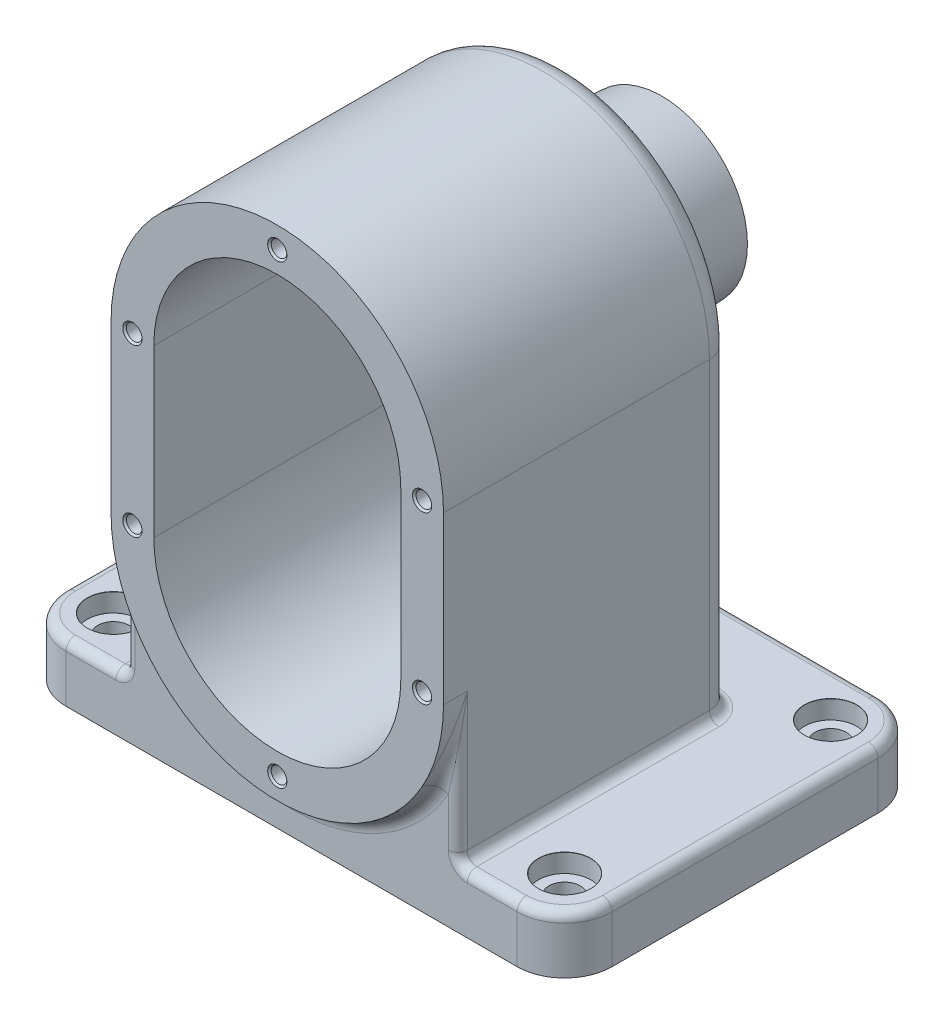
SolidWorks part; units mm, degrees
ref_plane "Front Plane" through (0, 0, 0) normal (0, 0, 1) x (1, 0, 0)
ref_plane "Top Plane" through (0, 0, 0) normal (0, 1, 0) x (1, 0, 0)
ref_plane "Right Plane" through (0, 0, 0) normal (1, 0, 0) x (0, 0, -1)
sketch "Sketch2" plane through (0, 0, 0) normal (0, 0, 1) x (1, 0, 0)
  line L0 (0, -17.5) -> (0, 17.5) construction
  line L1 (-35, -17.5) -> (-35, 17.5)
  line L2 (35, -17.5) -> (35, 17.5)
  arc A0 (-35, -17.5) -> (35, -17.5) centre (0, -17.5) ccw
  arc A1 (35, 17.5) -> (-35, 17.5) centre (0, 17.5) ccw
  point P2 (0, 0)
  dimension "D1" = 35
  dimension "D2" = 35
extrude "Boss-Extrude3" add sketch "Sketch2" along normal mid plane 58
shell "Shell9" thickness 9 removed face at (0, 0, 29)
sketch "Sketch3" plane through (0, 0, 0) normal (1, 0, 0) x (0, 0, -1)
  line L0 (29, 17.5) -> (49, 17.5)
  line L2 (29, -17.5) -> (29, 17.5) construction
  line L4 (49, -0.5) -> (49, 17.5)
  line L5 (29, -1.7644) -> (49, -0.5)
  line L6 (29, 17.5) -> (29, -1.7644)
  dimension "D1" = 18
  dimension "D2" = 20
revolve "Revolve1" add sketch "Sketch3" angle 360 about L0
sketch "Sketch4" plane through (0, 0, 0) normal (1, 0, 0) x (0, 0, -1)
  line L0 (20, 17.5) -> (20, 36.5489)
  line L1 (-29, 17.5) -> (29, 17.5) construction
  line L2 (20, 36.5489) -> (5, 35.5)
  line L3 (5, 35.5) -> (5, 17.5)
  line L4 (5, 17.5) -> (20, 17.5)
  line L5 (29, -1.7644) -> (29, 36.7644) construction
  line L6 (5, 35.5) -> (69.0806, 35.5) construction
  dimension "D1" = 9
  dimension "D2" = 18
  dimension "D3" = 15
  dimension "D4" = 4
revolve "Revolve2" add sketch "Sketch4" angle 360 about L4
sketch "Sketch5" plane through (0, 0, 0) normal (1, 0, 0) x (0, 0, -1)
  line L0 (20, -17.5) -> (20, -6.95)
  line L1 (-29, -17.5) -> (29, -17.5) construction
  line L2 (20, -6.95) -> (5, -8)
  line L3 (5, -8) -> (5, -17.5)
  line L4 (5, -17.5) -> (20, -17.5)
  line L5 (5, -8) -> (69.1367, -8) construction
  line L6 (29, -17.5) -> (29, 17.5) construction
  dimension "D1" = 9.5
  dimension "D2" = 15
  dimension "D3" = 10.55
  dimension "D4" = 9
revolve "Revolve4" add sketch "Sketch5" angle 360 about L4
sketch "Sketch6" plane through (0, 0, -49) normal (0, 0, -1) x (-1, 0, 0)
  circle A0 centre (0, 17.5) radius 14
  dimension "D1" = 28
extrude "Cut-Extrude1" cut sketch "Sketch6" against normal blind 15
sketch "Sketch7" plane through (0, 0, -34) normal (0, 0, -1) x (-1, 0, 0)
  circle A0 centre (0, 17.5) radius 10.5
  dimension "D1" = 21
extrude "Cut-Extrude2" cut sketch "Sketch7" against normal blind 6
sketch "Sketch8" plane through (0, 0, -28) normal (0, 0, -1) x (-1, 0, 0)
  circle A0 centre (0, 17.5) radius 9
  dimension "D1" = 18
extrude "Boss-Extrude4" add sketch "Sketch8" against normal blind 14.8
sketch "Sketch9" plane through (0, 0, -28) normal (0, 0, -1) x (-1, 0, 0)
  circle A0 centre (0, 17.5) radius 10.5
  dimension "D1" = 21
extrude "Cut-Extrude3" cut sketch "Sketch9" against normal blind 5
sketch "Sketch10" plane through (0, 0, -23) normal (0, 0, -1) x (-1, 0, 0)
  circle A0 centre (0, 17.5) radius 11
  dimension "D1" = 22
extrude "Cut-Extrude4" cut sketch "Sketch10" against normal blind 1.1
sketch "Sketch11" plane through (0, 0, -5) normal (0, 0, 1) x (1, 0, 0)
  circle A0 centre (0, 17.5) radius 10.5
  dimension "D1" = 21
extrude "Cut-Extrude5" cut sketch "Sketch11" against normal through all
sketch "Sketch12" plane through (0, 0, -5) normal (0, 0, 1) x (1, 0, 0)
  circle A0 centre (0, -17.5) radius 6
  dimension "D1" = 12
extrude "Cut-Extrude6" cut sketch "Sketch12" against normal through all both and the other way through all
sketch "Sketch15" plane through (0, 0, 29) normal (0, 0, 1) x (1, 0, 0)
  line L0 (26, -17.5) -> (26, 17.5) construction
  line L1 (-26, 17.5) -> (-26, -17.5) construction
  line L2 (35, -17.5) -> (35, 17.5)
  line L3 (-35, 17.5) -> (-35, -17.5)
  line L4 (35, -17.5) -> (35, 17.5)
  line L5 (-35, 17.5) -> (-35, -17.5)
  line L6 (26, -17.5) -> (26, 17.5)
  line L7 (-26, 17.5) -> (-26, -17.5)
  arc A0 (-26, -17.5) -> (26, -17.5) centre (0, -17.5) ccw construction
  arc A1 (26, 17.5) -> (-26, 17.5) centre (0, 17.5) ccw construction
  arc A2 (-35, -17.5) -> (35, -17.5) centre (0, -17.5) ccw
  arc A3 (35, 17.5) -> (-35, 17.5) centre (0, 17.5) ccw
  arc A4 (-35, -17.5) -> (35, -17.5) centre (0, -17.5) ccw
  arc A5 (35, 17.5) -> (-35, 17.5) centre (0, 17.5) ccw
  arc A6 (-26, -17.5) -> (26, -17.5) centre (0, -17.5) ccw
  arc A7 (26, 17.5) -> (-26, 17.5) centre (0, 17.5) ccw
  dimension "D1" = 0
extrude "Boss-Extrude6" add sketch "Sketch15" along normal blind 3
sketch "Sketch16" plane through (0, 0, 0) normal (1, 0, 0) x (0, 0, -1)
  line L0 (-32, 17.5) -> (29, 17.5) construction
  line L1 (-29, -48.5) -> (47, -48.5)
  line L2 (-29, -48.5) -> (-29, -60.5)
  line L3 (-29, -60.5) -> (47, -60.5)
  line L4 (47, -48.5) -> (47, -60.5)
  dimension "D1" = 3
  dimension "D2" = 76
  dimension "D3" = 12
  dimension "D4" = 66
extrude "Boss-Extrude7" add sketch "Sketch16" along normal mid plane 115
sketch "Sketch18" plane through (0, 0, -29) normal (0, 0, -1) x (-1, 0, 0)
  line L0 (-57.5, -48.5) -> (57.5, -48.5) construction
  line L1 (-35, -48.5) -> (35, -48.5)
  line L4 (-35, -17.5) -> (-35, -48.5)
  line L5 (35, -17.5) -> (35, -48.5)
  line L8 (-16.2481, -48.5) -> (16.2481, -48.5)
  line L9 (35, -17.5) -> (35, 17.5)
  line L10 (-35, 17.5) -> (-35, -17.5)
  line L11 (-16.2481, -48.5) -> (16.2481, -48.5)
  arc A3 (16.2481, -48.5) -> (35, -17.5) centre (0, -17.5) ccw
  arc A4 (35, 17.5) -> (-35, 17.5) centre (0, 17.5) ccw
  arc A5 (-35, -17.5) -> (-16.2481, -48.5) centre (0, -17.5) ccw
  arc A6 (16.2481, -48.5) -> (35, -17.5) centre (0, -17.5) ccw
  arc A8 (-35, -17.5) -> (-16.2481, -48.5) centre (0, -17.5) ccw
  arc M5 (16.2481, -48.5) -> (35, -17.5) centre (0, -17.5) ccw
  arc M9 (-35, -17.5) -> (-16.2481, -48.5) centre (0, -17.5) ccw
  dimension "D1" = 0
extrude "Boss-Extrude8" add sketch "Sketch18" against normal up to surface (58 mm away) contours L4 L1 M9 | L5 L1 M5 region at (29.7786, -41.2241, -29) region at (-29.7786, -41.2241, -29) up to face at (0, -53.1667, 29)
sketch "Sketch23" plane through (0, 0, -29) normal (0, 0, -1) x (-1, 0, 0)
  circle A0 centre (0, -17.5) radius 7.5
  circle A1 centre (0, -17.5) radius 6 construction
  circle A2 centre (0, -17.5) radius 6
  dimension "D1" = 15
extrude "Boss-Extrude9" add sketch "Sketch23" along normal blind 2
fillet "Fillet1" radius 10 4 edges at (-57.5, -54.5, -47) (-57.5, -54.5, 29) (57.5, -54.5, -47) (57.5, -54.5, 29)
hole_wizard "CBORE for M6 Cheese Head Screw1" positions "Sketch25" profile "Sketch26" counterbore size "M6" standard "ISO" end condition through all
sketch "Sketch25" plane through (0, -48.5, 0) normal (0, 1, 0) x (1, 0, 0)
  point P0 (-47.5, 37)
  point P3 (-47.5, -19)
  point P6 (47.5, -19)
  point P9 (47.5, 37)
sketch "Sketch26" plane through (-47.5, -48.5, -37) normal (1, 0, 0) x (0, 0, 1)
  line L0 (0, 0) -> (0, 12)
  line L1 (0, 12) -> (3.3, 12)
  line L3 (3.3, 12) -> (3.3, 3.9)
  line L4 (5.5, 3.9) -> (3.3, 3.9)
  line L5 (5.5, 3.9) -> (5.5, 0.025)
  line L6 (5.5, 0.025) -> (5.525, 0)
  line L7 (5.525, 0) -> (0, 0)
  line L8 (-5.5, 0.025) -> (-5.525, 0) construction
  line L11 (0, -6.35) -> (0, 107.95) construction
  dimension "Thru Hole Dia." = 6.6
  dimension "Thru Hole Depth" = 12
  dimension "C'Bore Dia." = 11
  dimension "C'Bore Depth" = 3.9
  dimension "Near C'Sink Dia." = 11.05
  dimension "Near C'Sink Angle" = 90
fillet "Fillet2" radius 5 3 edges at (35, -15.5, -29) (-35, -15.5, -29) (0, 52.5, -29)
fillet "Fillet3" radius 2 19 edges at (35, -33, 29) (-35, -33, 29) (41.25, -48.5, 29) (54.5711, -48.5, 26.0711) (57.5, -48.5, -9) (54.5711, -48.5, -44.0711) (-41.25, -48.5, 29) (-54.5711, -48.5, 26.0711) (-57.5, -48.5, -9) (-54.5711, -48.5, -44.0711) (-35, -48.5, 2.5) (-33.5355, -48.5, -27.5355) (35, -48.5, 2.5) (33.5355, -48.5, -27.5355) (10.55, -17.5, -20) (7.5, -17.5, -29) (19.2644, 17.5, -29) (0, -48.5, -47) (0, -48.5, -29)
sketch "Sketch27" plane through (0, 0, 32) normal (0, 0, 1) x (1, 0, 0)
  line L0 (0, 43.5) -> (0, 52.5)
  line L1 (-26, 17.5) -> (-35, 17.5)
  line L4 (26, 17.5) -> (35, 17.5)
  line L7 (0, -43.5) -> (0, -52.5)
  line L8 (-35, -17.5) -> (-26, -17.5)
  line L9 (26, -17.5) -> (35, -17.5)
  arc A0 (26, 17.5) -> (-26, 17.5) centre (0, 17.5) ccw construction
  arc A1 (35, 17.5) -> (-35, 17.5) centre (0, 17.5) ccw construction
  arc A2 (-26, -17.5) -> (26, -17.5) centre (0, -17.5) ccw construction
  arc A3 (-35, -17.5) -> (35, -17.5) centre (0, -17.5) ccw construction
  point P16 (0, 48)
  point P17 (-30.5, 17.5)
  point P18 (-30.5, -17.5)
  point P19 (0, -48)
  point P28 (30.5, -17.5)
  point P37 (30.5, 17.5)
hole_wizard "M4 Tapped Hole1" positions "3DSketch1" profile "Sketch29" tap size "M4" standard "ISO"
sketch3d "3DSketch1"
  point P0 (0, 48, 32)
  point P3 (30.5, 17.5, 32)
  point P6 (30.5, -17.5, 32)
  point P9 (0, -48, 32)
  point P12 (-30.5, -17.5, 32)
  point P15 (-30.5, 17.5, 32)
sketch "Sketch29" plane through (0, 48, 32) normal (1, 0, 0) x (0, -1, 0)
  line L0 (0, 0) -> (0, 13.9914)
  line L1 (0, 13.9914) -> (1.65, 13)
  line L2 (1.65, 13) -> (1.65, 0.375)
  line L3 (1.65, 0.375) -> (2.025, 0)
  line L5 (2.025, 0) -> (0, 0)
  line L6 (-1.65, 0.375) -> (-2.025, 0) construction
  line L10 (0, 13.9914) -> (-1.65, 13) construction
  line L11 (0, -6.35) -> (0, 107.95) construction
  dimension "Tap Drill Dia." = 3.3
  dimension "Tap Drill Depth" = 13
  dimension "Near C'Sink Dia." = 4.05
  dimension "Near C'Sink Angle" = 90
  dimension "Drill Angle" = 118
cosmetic thread "Hole Thread1" parameters "D1"=10, "D2"=4
cosmetic thread "Hole Thread2" parameters "D1"=10, "D2"=4
cosmetic thread "Hole Thread3" parameters "D1"=10, "D2"=4
cosmetic thread "Hole Thread4" parameters "D1"=10, "D2"=4
cosmetic thread "Hole Thread5" parameters "D1"=10, "D2"=4
cosmetic thread "Hole Thread6" parameters "D1"=10, "D2"=4
fillet "Fillet4" radius 3 3 edges at (34.1166, -25.3141, 28.6593) (-34.1166, -25.3141, 28.6593) (0, -52.5, 29)
